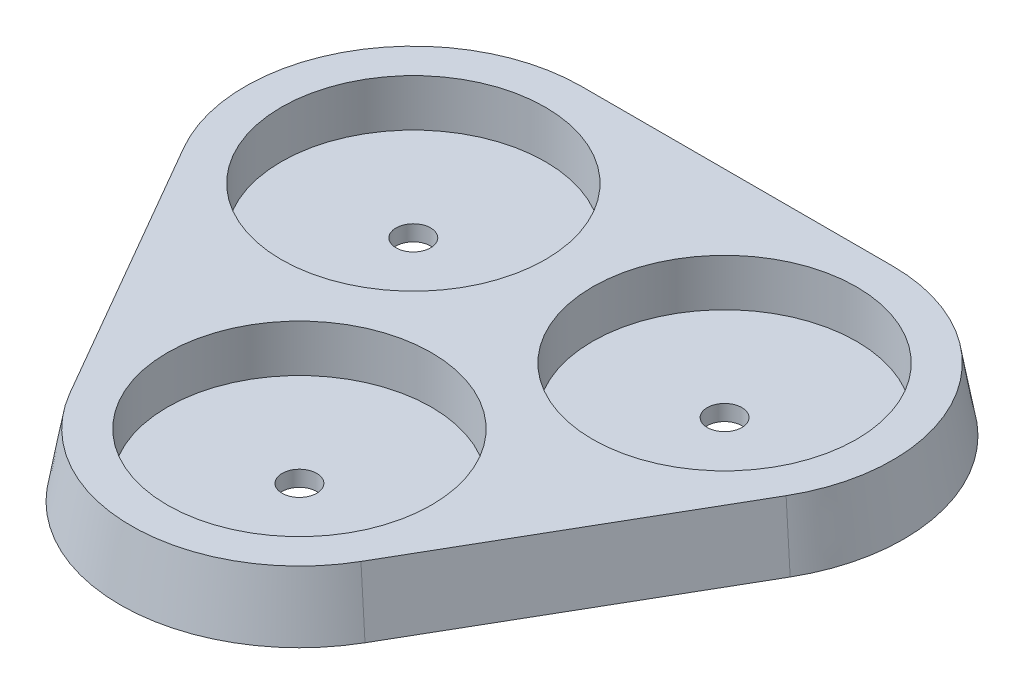
SolidWorks part; units mm, degrees
ref_plane "Front Plane" through (0, 0, 0) normal (0, 0, 1) x (1, 0, 0)
ref_plane "Top Plane" through (0, 0, 0) normal (0, 1, 0) x (1, 0, 0)
ref_plane "Right Plane" through (0, 0, 0) normal (1, 0, 0) x (0, 0, -1)
sketch "Sketch1" plane through (0, 0, 0) normal (0, 1, 0) x (1, 0, 0)
  line L0 (0, 0) -> (-9.9, -17.1473) construction
  line L1 (-9.9, -17.1473) -> (-19.8, 0) construction
  line L2 (-19.8, 0) -> (0, 0) construction
  line L3 (9.8727, -5.7) -> (-0.0273, -22.8473)
  line L4 (-19.7727, -22.8473) -> (-29.6727, -5.7)
  line L5 (0, 11.4) -> (-19.8, 11.4)
  circle A0 centre (0, 0) radius 8.4
  circle A1 centre (-19.8, 0) radius 8.4
  circle A2 centre (-9.9, -17.1473) radius 8.4
  circle A3 centre (-9.9, -17.1473) radius 1.1
  circle A4 centre (-19.8, 0) radius 1.1
  circle A5 centre (0, 0) radius 1.1
  circle A6 centre (-9.9, -17.1473) radius 11.4
  circle A7 centre (-19.8, 0) radius 11.4
  circle A8 centre (0, 0) radius 11.4
  dimension "D1" = 16.8
  dimension "D4" = 16.8
  dimension "D5" = 16.8
  dimension "D7" = 2.2
  dimension "D8" = 2.2
  dimension "D9" = 2.2
  dimension "D10" = 22.8
  dimension "D11" = 22.8
  dimension "D12" = 22.8
  dimension "D2" = 60
  dimension "D3" = 60
  dimension "D6" = 19.8
extrude "Boss-Extrude1" add sketch "Sketch1" along normal blind 4 draft 10 contours A7 L4 A6 | A8 A7 A6 A1 | A1 A4 | A8 L5 A7 | A8 A7 A0 A6 | A7 A8 | A8 A1 A6 A7 | A6 A7 | A7 A8 A6 A0 | A8 A6 A7 A2 | A8 A2 A7 A6 | A6 A8 | A0 A5 | A8 A6 L3 | A2 A3 | A4 | A3 | A5 | A8 A7 A6 region at (5.5209, 0, 9.6158) region at (3.5272, 0, 13.4679) region at (-9.9, 0, 28.2526) region at (-4.95, 0, 8.5737) region at (-23.3272, 0, 13.4679) region at (-9.9, 0, -9.7886) region at (-7.9651, 0, 4.5986) region at (-7.0689, 0, 4.0812) region at (-2.8311, 0, 13.0661) region at (-9.9, 0, 7.95) region at (-29.4025, 0, -5.544) region at (-14.85, 0, 8.5737) region at (-9.9, 0, 0) region at (-9.9, 0, 5.7158) region at (-26.8689, 0, -4.0812) region at (-11.8349, 0, 4.5986) region at (-9.9, 0, 17.1473) region at (-19.8, 0, 0) region at (0, 0, 0)
extrude "Cut-Extrude1" cut sketch "Sketch1<3>" against normal blind 4 from surface contours A3 | A5 | A4 region at (-9.9, 0, 17.1473) region at (0, 0, 0) starting at face at (-9.9, 4, 5.7158)
sketch "Sketch1<3>" plane through (0, 0, 0) normal (0, 1, 0) x (1, 0, 0) same geometry as "Sketch1"
extrude "Cut-Extrude2" cut sketch "Sketch1<4>" against normal blind 3 from surface contours A1 A4 | A2 A3 | A0 A5 region at (-7.0689, 0, 4.0812) region at (-2.8311, 0, 13.0661) region at (-26.8689, 0, -4.0812) starting at face at (-9.9, 4, 18.2473)
sketch "Sketch1<4>" plane through (0, 0, 0) normal (0, 1, 0) x (1, 0, 0) same geometry as "Sketch1"
